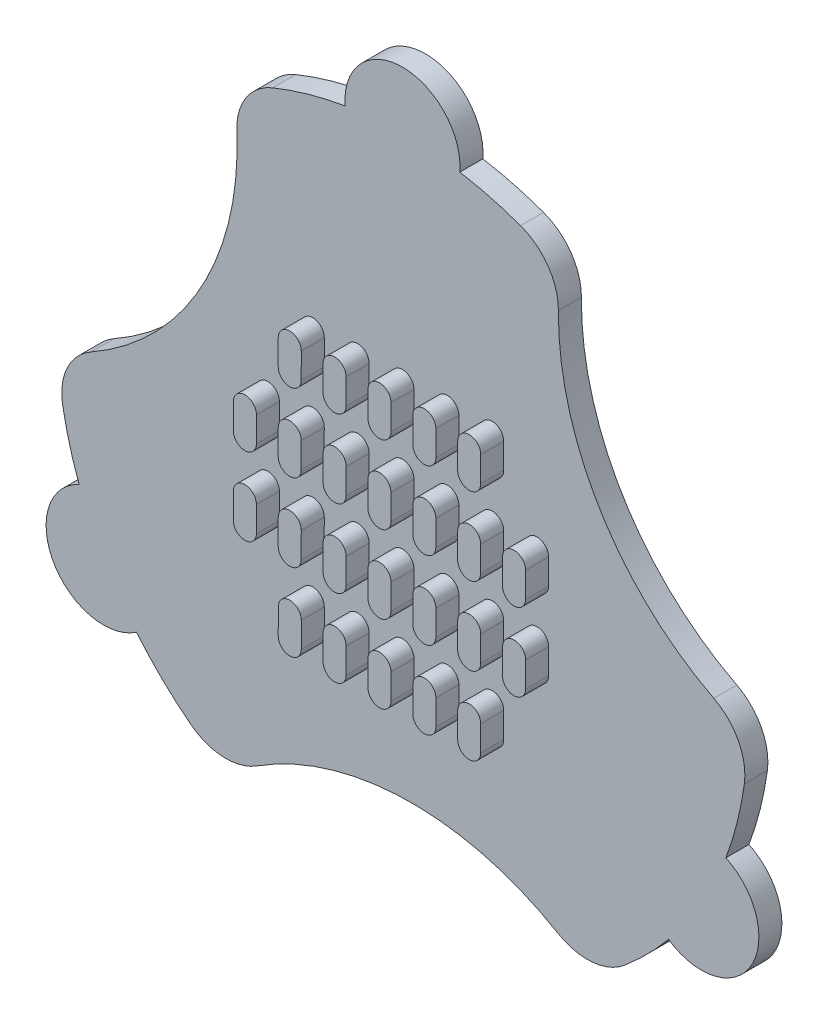
SolidWorks part; units mm, degrees
ref_plane "Спереди" through (0, 0, 0) normal (0, 0, 1) x (1, 0, 0)
ref_plane "Сверху" through (0, 0, 0) normal (0, 1, 0) x (1, 0, 0)
ref_plane "Справа" through (0, 0, 0) normal (1, 0, 0) x (0, 0, -1)
sketch "Sketch1" plane through (0, 0, 0) normal (0, 0, 1) x (1, 0, 0)
  line L0 (3.9, 6.755) -> (7.8, 0) construction
  line L2 (5.85, 10.1325) -> (11.7, 0) construction
  line L4 (7.8, 13.51) -> (15.6, 0) construction
  circle A61 centre (0, 0) radius 20
  circle A131 centre (0, 0) radius 1.25
  circle A484 centre (3.9, 0) radius 1.25
  circle A485 centre (7.8, 0) radius 1.25
  circle A486 centre (11.7, 0) radius 1.25
  circle A487 centre (15.6, 0) radius 1.25
  circle A488 centre (1.95, -3.3775) radius 1.25
  circle A489 centre (3.9, -6.755) radius 1.25
  circle A490 centre (5.85, -10.1325) radius 1.25
  circle A491 centre (7.8, -13.51) radius 1.25
  circle A492 centre (-1.95, -3.3775) radius 1.25
  circle A493 centre (-3.9, -6.755) radius 1.25
  circle A494 centre (-5.85, -10.1325) radius 1.25
  circle A495 centre (-7.8, -13.51) radius 1.25
  circle A496 centre (-3.9, 0) radius 1.25
  circle A497 centre (-7.8, 0) radius 1.25
  circle A498 centre (-11.7, 0) radius 1.25
  circle A499 centre (-15.6, 0) radius 1.25
  circle A500 centre (-1.95, 3.3775) radius 1.25
  circle A501 centre (-3.9, 6.755) radius 1.25
  circle A502 centre (-5.85, 10.1325) radius 1.25
  circle A503 centre (-7.8, 13.51) radius 1.25
  circle A504 centre (1.95, 3.3775) radius 1.25
  circle A505 centre (3.9, 6.755) radius 1.25
  circle A506 centre (5.85, 10.1325) radius 1.25
  circle A507 centre (7.8, 13.51) radius 1.25
  circle A508 centre (5.85, 3.3775) radius 1.25
  circle A509 centre (7.8, 6.755) radius 1.25
  circle A510 centre (9.75, 3.3775) radius 1.25
  circle A511 centre (11.7, 6.755) radius 1.25
  circle A512 centre (9.7491, 10.1341) radius 1.25
  circle A513 centre (13.6509, 3.3759) radius 1.25
  circle A514 centre (5.85, -3.3791) radius 1.25
  circle A515 centre (9.75, -3.3791) radius 1.25
  circle A516 centre (7.8, -6.7566) radius 1.25
  circle A517 centre (11.7, -6.7566) radius 1.25
  circle A518 centre (9.7491, -10.1356) radius 1.25
  circle A519 centre (13.6509, -3.3775) radius 1.25
  circle A520 centre (-0.0013, -6.7573) radius 1.25
  circle A521 centre (1.9487, -10.1348) radius 1.25
  circle A522 centre (-1.9513, -10.1348) radius 1.25
  circle A523 centre (-0.0013, -13.5123) radius 1.25
  circle A524 centre (-3.9032, -13.5123) radius 1.25
  circle A525 centre (3.9005, -13.5123) radius 1.25
  circle A526 centre (-5.8527, -3.3791) radius 1.25
  circle A527 centre (-7.8027, -6.7566) radius 1.25
  circle A528 centre (-9.7527, -3.3791) radius 1.25
  circle A529 centre (-11.7027, -6.7566) radius 1.25
  circle A530 centre (-13.6536, -3.3775) radius 1.25
  circle A531 centre (-9.7518, -10.1356) radius 1.25
  circle A532 centre (-5.8527, 3.3775) radius 1.25
  circle A533 centre (-9.7527, 3.3775) radius 1.25
  circle A534 centre (-7.8027, 6.755) radius 1.25
  circle A535 centre (-11.7027, 6.755) radius 1.25
  circle A536 centre (-9.7518, 10.1341) radius 1.25
  circle A537 centre (-13.6536, 3.3759) radius 1.25
  circle A538 centre (-0.0014, 6.7558) radius 1.25
  circle A539 centre (-1.9514, 10.1333) radius 1.25
  circle A540 centre (1.9486, 10.1333) radius 1.25
  circle A541 centre (-0.0014, 13.5108) radius 1.25
  circle A542 centre (3.9005, 13.5108) radius 1.25
  circle A543 centre (-3.9032, 13.5108) radius 1.25
  circle A544 centre (13.65, -1.1258) radius 2.2517 construction
  circle A545 centre (11.7009, -4.5044) radius 2.2522 construction
  circle A546 centre (9.75, -7.8834) radius 2.2522 construction
  circle A547 centre (7.7987, -11.2591) radius 2.2509 construction
  circle A548 centre (13.65, -1.1258) radius 0.65
  circle A549 centre (11.7009, -4.5044) radius 0.65
  circle A550 centre (9.75, -7.8834) radius 0.65
  circle A551 centre (7.7987, -11.2591) radius 0.65
  circle A552 centre (9.75, -1.1258) radius 0.65
  circle A553 centre (7.8009, -4.5044) radius 0.65
  circle A554 centre (5.85, -7.8834) radius 0.65
  circle A555 centre (3.8987, -11.2591) radius 0.65
  circle A556 centre (5.85, -1.1258) radius 0.65
  circle A557 centre (3.9009, -4.5044) radius 0.65
  circle A558 centre (1.95, -7.8834) radius 0.65
  circle A559 centre (-0.0013, -11.2591) radius 0.65
  circle A560 centre (1.95, -1.1258) radius 0.65
  circle A561 centre (0.0009, -4.5044) radius 0.65
  circle A562 centre (-1.95, -7.8834) radius 0.65
  circle A563 centre (-3.9013, -11.2591) radius 0.65
  circle A564 centre (-1.95, -1.1258) radius 0.65
  circle A565 centre (-3.8991, -4.5044) radius 0.65
  circle A566 centre (-5.85, -7.8834) radius 0.65
  circle A567 centre (-7.8013, -11.2591) radius 0.65
  circle A568 centre (-5.85, -1.1258) radius 0.65
  circle A569 centre (-7.7991, -4.5044) radius 0.65
  circle A570 centre (-9.75, -7.8834) radius 0.65
  circle A572 centre (-9.75, -1.1258) radius 0.65
  circle A573 centre (-11.6991, -4.5044) radius 0.65
  circle A576 centre (-13.65, -1.1258) radius 0.65
  circle A587 centre (0, 2.2517) radius 2.2517 construction
  circle A588 centre (0, 2.2517) radius 0.65
  circle A589 centre (3.9, 2.2517) radius 0.65
  circle A590 centre (7.8, 2.2517) radius 0.65
  circle A591 centre (11.7, 2.2517) radius 0.65
  circle A592 centre (15.6, 2.2517) radius 0.65
  circle A593 centre (1.9491, 5.6297) radius 2.2522 construction
  circle A594 centre (1.9491, 5.6297) radius 0.65
  circle A595 centre (5.8491, 5.6297) radius 0.65
  circle A596 centre (9.7491, 5.6297) radius 0.65
  circle A597 centre (13.6491, 5.6297) radius 0.65
  circle A598 centre (3.8991, 9.0072) radius 2.2522 construction
  circle A599 centre (3.8991, 9.0072) radius 0.65
  circle A600 centre (7.7991, 9.0072) radius 0.65
  circle A601 centre (11.6991, 9.0072) radius 0.65
  circle A602 centre (5.85, 12.3842) radius 2.2517 construction
  circle A603 centre (5.85, 12.3842) radius 0.65
  circle A604 centre (9.75, 12.3842) radius 0.65
  circle A605 centre (5.85, -14.6358) radius 0.65
  circle A606 centre (1.9509, -14.6353) radius 0.65
  circle A607 centre (-1.9491, -14.6353) radius 0.65
  circle A608 centre (-5.85, -14.6358) radius 0.65
  circle A609 centre (-15.6, 2.2517) radius 0.65
  circle A610 centre (-13.65, 5.6281) radius 0.65
  circle A611 centre (-11.7, 9.0056) radius 0.65
  circle A612 centre (-9.75, 12.3842) radius 0.65
  circle A613 centre (-5.85, 12.3842) radius 0.65
  circle A614 centre (-1.95, 12.3842) radius 0.65
  circle A615 centre (1.95, 12.3842) radius 0.65
  circle A616 centre (-7.8, 9.0056) radius 0.65
  circle A617 centre (-9.75, 5.6281) radius 0.65
  circle A618 centre (-11.7, 2.2517) radius 0.65
  circle A619 centre (-3.9, 9.0056) radius 0.65
  circle A620 centre (-5.85, 5.6281) radius 0.65
  circle A621 centre (-7.8, 2.2517) radius 0.65
  circle A622 centre (0, 9.0056) radius 0.65
  circle A623 centre (-1.95, 5.6281) radius 0.65
  circle A624 centre (-3.9, 2.2517) radius 0.65
  circle A625 centre (-15.5991, -4.5044) radius 0.65
  circle A626 centre (-13.65, -7.8834) radius 0.65
  circle A627 centre (-17.55, -7.8834) radius 0.65
  circle A628 centre (-19.5013, -11.2591) radius 0.65
  circle A629 centre (-15.6013, -11.2591) radius 0.65
  circle A630 centre (-11.7013, -11.2591) radius 0.65
  point P51 (0, 0)
  point P125 (-0.0013, -0.0008)
  point P231 (0, 0)
  dimension "D1" = 5
  dimension "D3" = 6
  dimension "D5" = 8
  dimension "D7" = 4
  dimension "D11" = 4
  dimension "D2" = 6
  dimension "D6" = 5
  dimension "D8" = 3
  dimension "D9" = 2
  dimension "D4" = 1.3
  dimension "D10" = 3
ref_plane "Plane1" through (0, 0, 10) normal (0, 0, 1) x (1, 0, 0)
sketch "Sketch2" plane through (0, 0, 10) normal (0, 0, 1) x (1, 0, 0)
  line L0 (-7.8, 13.51) -> (-7.8027, 6.755) construction
  line L1 (-9.7518, 10.1341) -> (-5.85, 10.1325) construction
  line L2 (-7.8009, 11.2325) -> (-7.8018, 9.0325) construction
  line L3 (-6.8009, 11.2321) -> (-6.8018, 9.0321)
  line L4 (-8.8009, 11.2329) -> (-8.8018, 9.0329)
  line L5 (-4.9009, 11.2329) -> (-4.9018, 9.0329)
  line L6 (-2.9009, 11.2321) -> (-2.9018, 9.0321)
  line L7 (-3.9009, 11.2325) -> (-3.9018, 9.0325) construction
  line L8 (-1.0009, 11.2329) -> (-1.0018, 9.0329)
  line L9 (0.9991, 11.2321) -> (0.9982, 9.0321)
  line L10 (-0.0009, 11.2325) -> (-0.0018, 9.0325) construction
  line L11 (2.8991, 11.2329) -> (2.8982, 9.0329)
  line L12 (4.8991, 11.2321) -> (4.8982, 9.0321)
  line L13 (3.8991, 11.2325) -> (3.8982, 9.0325) construction
  line L14 (6.7991, 11.2329) -> (6.7982, 9.0329)
  line L15 (8.7991, 11.2321) -> (8.7982, 9.0321)
  line L16 (7.7991, 11.2325) -> (7.7982, 9.0325) construction
  line L17 (-9.7518, 10.1341) -> (-9.7527, 3.3775) construction
  line L18 (-11.7027, 6.755) -> (-7.8027, 6.755) construction
  line L19 (-10.7033, 2.2767) -> (-10.7014, 4.4767)
  line L22 (-9.7527, 3.3775) -> (-5.8527, 3.3775) construction
  line L25 (-7.8027, 6.755) -> (-7.8, 0) construction
  line L26 (-7.8036, 2.2775) -> (-7.8018, 4.4775) construction
  line L27 (-8.8036, 2.2783) -> (-8.8018, 4.4783)
  line L28 (-6.8036, 2.2767) -> (-6.8018, 4.4767)
  line L29 (-2.9036, 2.2767) -> (-2.9018, 4.4767)
  line L30 (-4.9036, 2.2783) -> (-4.9018, 4.4783)
  line L31 (-3.9036, 2.2775) -> (-3.9018, 4.4775) construction
  line L32 (0.9964, 2.2767) -> (0.9982, 4.4767)
  line L33 (-1.0036, 2.2783) -> (-1.0018, 4.4783)
  line L34 (-0.0036, 2.2775) -> (-0.0018, 4.4775) construction
  line L35 (4.8964, 2.2767) -> (4.8982, 4.4767)
  line L36 (2.8964, 2.2783) -> (2.8982, 4.4783)
  line L37 (3.8964, 2.2775) -> (3.8982, 4.4775) construction
  line L38 (8.7964, 2.2767) -> (8.7982, 4.4767)
  line L39 (6.7964, 2.2783) -> (6.7982, 4.4783)
  line L40 (7.7964, 2.2775) -> (7.7982, 4.4775) construction
  line L41 (12.6964, 2.2767) -> (12.6982, 4.4767)
  line L42 (10.6964, 2.2783) -> (10.6982, 4.4783)
  line L43 (11.6964, 2.2775) -> (11.6982, 4.4775) construction
  line L44 (-12.7033, 2.2783) -> (-12.7014, 4.4783)
  line L45 (-11.7033, 2.2775) -> (-11.7014, 4.4775) construction
  line L46 (-9.7527, -3.3791) -> (-5.8527, -3.3791) construction
  line L47 (-7.8, 0) -> (-7.8027, -6.7566) construction
  line L48 (-7.8045, -4.4791) -> (-7.8009, -2.2791) construction
  line L49 (-8.8045, -4.4774) -> (-8.8009, -2.2774)
  line L50 (-6.8045, -4.4807) -> (-6.8009, -2.2807)
  line L51 (-2.9045, -4.4807) -> (-2.9009, -2.2807)
  line L52 (-4.9045, -4.4774) -> (-4.9009, -2.2774)
  line L53 (-3.9045, -4.4791) -> (-3.9009, -2.2791) construction
  line L54 (0.9955, -4.4807) -> (0.9991, -2.2807)
  line L55 (-1.0045, -4.4774) -> (-1.0009, -2.2774)
  line L56 (-0.0045, -4.4791) -> (-0.0009, -2.2791) construction
  line L57 (4.8955, -4.4807) -> (4.8991, -2.2807)
  line L58 (2.8955, -4.4774) -> (2.8991, -2.2774)
  line L59 (3.8955, -4.4791) -> (3.8991, -2.2791) construction
  line L60 (8.7955, -4.4807) -> (8.7991, -2.2807)
  line L61 (6.7955, -4.4774) -> (6.7991, -2.2774)
  line L62 (7.7955, -4.4791) -> (7.7991, -2.2791) construction
  line L63 (12.6955, -4.4807) -> (12.6991, -2.2807)
  line L64 (10.6955, -4.4774) -> (10.6991, -2.2774)
  line L65 (11.6955, -4.4791) -> (11.6991, -2.2791) construction
  line L66 (-10.7041, -4.4807) -> (-10.7006, -2.2807)
  line L67 (-12.7041, -4.4774) -> (-12.7005, -2.2774)
  line L68 (-11.7041, -4.4791) -> (-11.7006, -2.2791) construction
  line L69 (-9.7518, -10.1356) -> (-5.482, -10.1356) construction
  line L70 (-7.8027, -6.7566) -> (-7.8, -13.51) construction
  line L71 (-7.8004, -9.0356) -> (-7.8009, -11.2356) construction
  line L72 (-6.8004, -9.0358) -> (-6.8009, -11.2358)
  line L73 (-8.8004, -9.0354) -> (-8.8009, -11.2354)
  line L74 (-4.9004, -9.0354) -> (-4.9009, -11.2354)
  line L75 (-2.9004, -9.0358) -> (-2.9009, -11.2358)
  line L76 (-3.9004, -9.0356) -> (-3.9009, -11.2356) construction
  line L77 (-1.0004, -9.0354) -> (-1.0009, -11.2354)
  line L78 (0.9996, -9.0358) -> (0.9991, -11.2358)
  line L79 (-0.0004, -9.0356) -> (-0.0009, -11.2356) construction
  line L80 (2.8996, -9.0354) -> (2.8991, -11.2354)
  line L81 (4.8996, -9.0358) -> (4.8991, -11.2358)
  line L82 (3.8996, -9.0356) -> (3.8991, -11.2356) construction
  line L83 (6.7996, -9.0354) -> (6.7991, -11.2354)
  line L84 (8.7996, -9.0358) -> (8.7991, -11.2358)
  line L85 (7.7996, -9.0356) -> (7.7991, -11.2356) construction
  arc A0 (-6.8009, 11.2321) -> (-8.8009, 11.2329) centre (-7.8009, 11.2325) ccw
  arc A1 (-8.8018, 9.0329) -> (-6.8018, 9.0321) centre (-7.8018, 9.0325) ccw
  arc A2 (-2.9009, 11.2321) -> (-4.9009, 11.2329) centre (-3.9009, 11.2325) ccw
  arc A3 (-4.9018, 9.0329) -> (-2.9018, 9.0321) centre (-3.9018, 9.0325) ccw
  arc A4 (0.9991, 11.2321) -> (-1.0009, 11.2329) centre (-0.0009, 11.2325) ccw
  arc A5 (-1.0018, 9.0329) -> (0.9982, 9.0321) centre (-0.0018, 9.0325) ccw
  arc A6 (4.8991, 11.2321) -> (2.8991, 11.2329) centre (3.8991, 11.2325) ccw
  arc A7 (2.8982, 9.0329) -> (4.8982, 9.0321) centre (3.8982, 9.0325) ccw
  arc A8 (8.7991, 11.2321) -> (6.7991, 11.2329) centre (7.7991, 11.2325) ccw
  arc A9 (6.7982, 9.0329) -> (8.7982, 9.0321) centre (7.7982, 9.0325) ccw
  arc A14 (-8.8036, 2.2783) -> (-6.8036, 2.2767) centre (-7.8036, 2.2775) ccw
  arc A15 (-6.8018, 4.4767) -> (-8.8018, 4.4783) centre (-7.8018, 4.4775) ccw
  arc A16 (-4.9036, 2.2783) -> (-2.9036, 2.2767) centre (-3.9036, 2.2775) ccw
  arc A17 (-2.9018, 4.4767) -> (-4.9018, 4.4783) centre (-3.9018, 4.4775) ccw
  arc A18 (-1.0036, 2.2783) -> (0.9964, 2.2767) centre (-0.0036, 2.2775) ccw
  arc A19 (0.9982, 4.4767) -> (-1.0018, 4.4783) centre (-0.0018, 4.4775) ccw
  arc A20 (2.8964, 2.2783) -> (4.8964, 2.2767) centre (3.8964, 2.2775) ccw
  arc A21 (4.8982, 4.4767) -> (2.8982, 4.4783) centre (3.8982, 4.4775) ccw
  arc A22 (6.7964, 2.2783) -> (8.7964, 2.2767) centre (7.7964, 2.2775) ccw
  arc A23 (8.7982, 4.4767) -> (6.7982, 4.4783) centre (7.7982, 4.4775) ccw
  arc A24 (10.6964, 2.2783) -> (12.6964, 2.2767) centre (11.6964, 2.2775) ccw
  arc A25 (12.6982, 4.4767) -> (10.6982, 4.4783) centre (11.6982, 4.4775) ccw
  arc A26 (-12.7033, 2.2783) -> (-10.7033, 2.2767) centre (-11.7033, 2.2775) ccw
  arc A27 (-10.7014, 4.4767) -> (-12.7014, 4.4783) centre (-11.7014, 4.4775) ccw
  arc A28 (-8.8045, -4.4774) -> (-6.8045, -4.4807) centre (-7.8045, -4.4791) ccw
  arc A29 (-6.8009, -2.2807) -> (-8.8009, -2.2774) centre (-7.8009, -2.2791) ccw
  arc A30 (-4.9045, -4.4774) -> (-2.9045, -4.4807) centre (-3.9045, -4.4791) ccw
  arc A31 (-2.9009, -2.2807) -> (-4.9009, -2.2774) centre (-3.9009, -2.2791) ccw
  arc A32 (-1.0045, -4.4774) -> (0.9955, -4.4807) centre (-0.0045, -4.4791) ccw
  arc A33 (0.9991, -2.2807) -> (-1.0009, -2.2774) centre (-0.0009, -2.2791) ccw
  arc A34 (2.8955, -4.4774) -> (4.8955, -4.4807) centre (3.8955, -4.4791) ccw
  arc A35 (4.8991, -2.2807) -> (2.8991, -2.2774) centre (3.8991, -2.2791) ccw
  arc A36 (6.7955, -4.4774) -> (8.7955, -4.4807) centre (7.7955, -4.4791) ccw
  arc A37 (8.7991, -2.2807) -> (6.7991, -2.2774) centre (7.7991, -2.2791) ccw
  arc A38 (10.6955, -4.4774) -> (12.6955, -4.4807) centre (11.6955, -4.4791) ccw
  arc A39 (12.6991, -2.2807) -> (10.6991, -2.2774) centre (11.6991, -2.2791) ccw
  arc A40 (-12.7041, -4.4774) -> (-10.7041, -4.4807) centre (-11.7041, -4.4791) ccw
  arc A41 (-10.7006, -2.2807) -> (-12.7005, -2.2774) centre (-11.7006, -2.2791) ccw
  arc A42 (-6.8004, -9.0358) -> (-8.8004, -9.0354) centre (-7.8004, -9.0356) ccw
  arc A43 (-8.8009, -11.2354) -> (-6.8009, -11.2358) centre (-7.8009, -11.2356) ccw
  arc A44 (-2.9004, -9.0358) -> (-4.9004, -9.0354) centre (-3.9004, -9.0356) ccw
  arc A45 (-4.9009, -11.2354) -> (-2.9009, -11.2358) centre (-3.9009, -11.2356) ccw
  arc A46 (0.9996, -9.0358) -> (-1.0004, -9.0354) centre (-0.0004, -9.0356) ccw
  arc A47 (-1.0009, -11.2354) -> (0.9991, -11.2358) centre (-0.0009, -11.2356) ccw
  arc A48 (4.8996, -9.0358) -> (2.8996, -9.0354) centre (3.8996, -9.0356) ccw
  arc A49 (2.8991, -11.2354) -> (4.8991, -11.2358) centre (3.8991, -11.2356) ccw
  arc A50 (8.7996, -9.0358) -> (6.7996, -9.0354) centre (7.7996, -9.0356) ccw
  arc A51 (6.7991, -11.2354) -> (8.7991, -11.2358) centre (7.7991, -11.2356) ccw
  circle A52 centre (0, 0) radius 16.85 construction
  circle A53 centre (0, 0) radius 18.85
  point P10 (-7.8014, 10.1325)
  point P18 (-3.9014, 10.1325)
  point P25 (-0.0014, 10.1325)
  point P32 (3.8986, 10.1325)
  point P39 (7.7986, 10.1325)
  point P50 (-11.7023, 3.3775)
  point P58 (-7.8027, 3.3775)
  point P68 (-3.9027, 3.3775)
  point P75 (-0.0027, 3.3775)
  point P82 (3.8973, 3.3775)
  point P89 (7.7973, 3.3775)
  point P96 (11.6973, 3.3775)
  point P108 (-7.8027, -3.3791)
  point P116 (-3.9027, -3.3791)
  point P123 (-0.0027, -3.3791)
  point P130 (3.8973, -3.3791)
  point P137 (7.7973, -3.3791)
  point P144 (11.6973, -3.3791)
  point P151 (-11.7023, -3.3791)
  point P162 (-7.8007, -10.1356)
  point P170 (-3.9007, -10.1356)
  point P177 (-0.0007, -10.1356)
  point P184 (3.8993, -10.1356)
  point P191 (7.7993, -10.1356)
  point P199 (0, 0)
  dimension "D1" = 2
  dimension "D15" = 2
  dimension "D2" = 2.2
  dimension "D4" = 2
  dimension "D5" = 2.2
  dimension "D6" = 2
  dimension "D7" = 2.2
  dimension "D9" = 2
  dimension "D12" = 2.2
  dimension "D13" = 2
  dimension "D3" = 5
  dimension "D8" = 6
  dimension "D10" = 6
  dimension "D11" = 2
  dimension "D14" = 5
extrude "Boss-Extrude1" add sketch "Sketch2" along normal blind 2
sketch "Sketch3" plane through (0, 0, 12) normal (0, 0, 1) x (1, 0, 0)
  circle A0 centre (0, 0) radius 17.6
  circle A1 centre (0, 0) radius 30
extrude "Boss-Extrude2" add sketch "Sketch3" against normal blind 2
sketch "Sketch4" plane through (0, 0, 12) normal (0, 0, 1) x (1, 0, 0)
  circle A0 centre (0, 0) radius 25 construction
  circle A1 centre (0, 25) radius 2.9
  circle A2 centre (21.6506, -12.5) radius 2.9
  circle A3 centre (-21.6506, -12.5) radius 2.9
  point P11 (0, 0)
  dimension "D1" = 3
sketch "Sketch6" plane through (0, 0, 10) normal (0, 0, -1) x (-1, 0, 0)
  circle A0 centre (0, 30) radius 5
  circle A1 centre (0, 0) radius 30 construction
  circle A2 centre (25.9808, -15) radius 5
  circle A3 centre (-25.9808, -15) radius 5
  point P10 (0, 0)
  dimension "D1" = 3
extrude "Boss-Extrude4" add sketch "Sketch6" against normal blind 2
sketch "Sketch5" plane through (0, 0, 10) normal (0, 0, -1) x (-1, 0, 0)
  circle A0 centre (0, 25) radius 3
  circle A1 centre (21.6506, -12.5) radius 3
  circle A2 centre (-21.6506, -12.5) radius 3
sketch "Sketch7" plane through (0, 0, 10) normal (0, 0, -1) x (-1, 0, 0)
  line L0 (0, 0) -> (-38.5501, 23.214) construction
  circle A0 centre (0, 0) radius 45 construction
  circle A1 centre (-38.5501, 23.214) radius 25
  circle A2 centre (39.379, 21.7783) radius 25
  circle A3 centre (-0.8289, -44.9924) radius 25
  circle A4 centre (0, 0) radius 19 construction
  point P11 (0, 0)
  dimension "D1" = 3
extrude "Cut-Extrude2" cut sketch "Sketch7" against normal blind 2
fillet "Fillet1" radius 5 6 edges at (-14.7586, 26.1186, 11) (-29.9681, -1.3827, 11) (-15.2401, -25.8407, 11) (16.1815, -25.2618, 11) (29.9987, -0.278, 11) (13.7866, 26.6445, 11)
extrude "Boss-Extrude5" add sketch "Sketch2<2>" along normal blind 4 contours L4 A1 L3 A0 | L5 A3 L6 A2 | L8 A5 L9 A4 | L11 A7 L12 A6 | L19 A27 L44 A26 | L28 A15 L27 A14 | L29 A17 L30 A16 | L32 A19 L33 A18 | L35 A21 L36 A20 | L38 A23 L39 A22 | L41 A25 L42 A24 | L66 A41 L67 A40 | L50 A29 L49 A28 | L51 A31 L52 A30 | L54 A33 L55 A32 | L60 A37 L61 A36 | L63 A39 L64 A38 | L83 A51 L84 A50 | L80 A49 L81 A48 | L77 A47 L78 A46 | L74 A45 L75 A44 | L73 A43 L72 A42 | L15 A9 L14 A8 | L57 A35 L58 A34 region at (-7.8014, 10.1325, 10) region at (-3.9014, 10.1325, 10) region at (-0.0014, 10.1325, 10) region at (3.8986, 10.1325, 10) region at (-11.7023, 3.3775, 10) region at (-7.8027, 3.3775, 10) region at (-3.9027, 3.3775, 10) region at (-0.0027, 3.3775, 10) region at (3.8973, 3.3775, 10) region at (7.7973, 3.3775, 10) region at (11.6973, 3.3775, 10) region at (-7.8027, -3.3791, 10) region at (-3.9027, -3.3791, 10) region at (-0.0027, -3.3791, 10) region at (7.7973, -3.3791, 10) region at (11.6973, -3.3791, 10) region at (-11.7023, -3.3791, 10) region at (-7.8007, -10.1356, 10) region at (-3.9007, -10.1356, 10) region at (-0.0007, -10.1356, 10) region at (3.8993, -10.1356, 10) region at (7.7993, -10.1356, 10)
sketch "Sketch2<2>" plane through (0, 0, 10) normal (0, 0, 1) x (1, 0, 0) same geometry as "Sketch2"
sketch "Sketch8" plane through (0, 0, 13) normal (0, 0, 1) x (1, 0, 0)
  line L0 (0, 0) -> (6.0128, 0) construction
  line L1 (-9.7495, -6.7926) -> (9.7495, -6.7926)
  line L2 (0, 0) -> (0, 5.1095) construction
  line L3 (-9.7495, 13.4736) -> (9.7495, 13.4736)
  line L4 (-9.7495, 13.4736) -> (-9.7495, 6.7926)
  line L5 (-9.7495, 6.7926) -> (9.7495, 6.7926)
  line L6 (9.7495, 13.4736) -> (9.7495, 6.7926)
  line L7 (-9.7495, 13.4736) -> (9.7495, 6.7926) construction
  line L8 (-9.7495, 6.7926) -> (9.7495, 13.4736) construction
  line L9 (-13.6953, -6.7926) -> (13.6953, -6.7926)
  line L10 (-13.6953, -6.7926) -> (-13.6953, 6.7926)
  line L11 (-13.6953, 6.7926) -> (13.6953, 6.7926)
  line L12 (13.6953, -6.7926) -> (13.6953, 6.7926)
  line L13 (-13.6953, -6.7926) -> (13.6953, 6.7926) construction
  line L14 (-13.6953, 6.7926) -> (13.6953, -6.7926) construction
  line L15 (9.7495, -13.4736) -> (9.7495, -6.7926)
  line L16 (-9.7495, -13.4736) -> (9.7495, -13.4736)
  line L17 (-9.7495, -13.4736) -> (-9.7495, -6.7926)
  circle A0 centre (0, 0) radius 20.5111
  point P3 (0, 10.1331)
